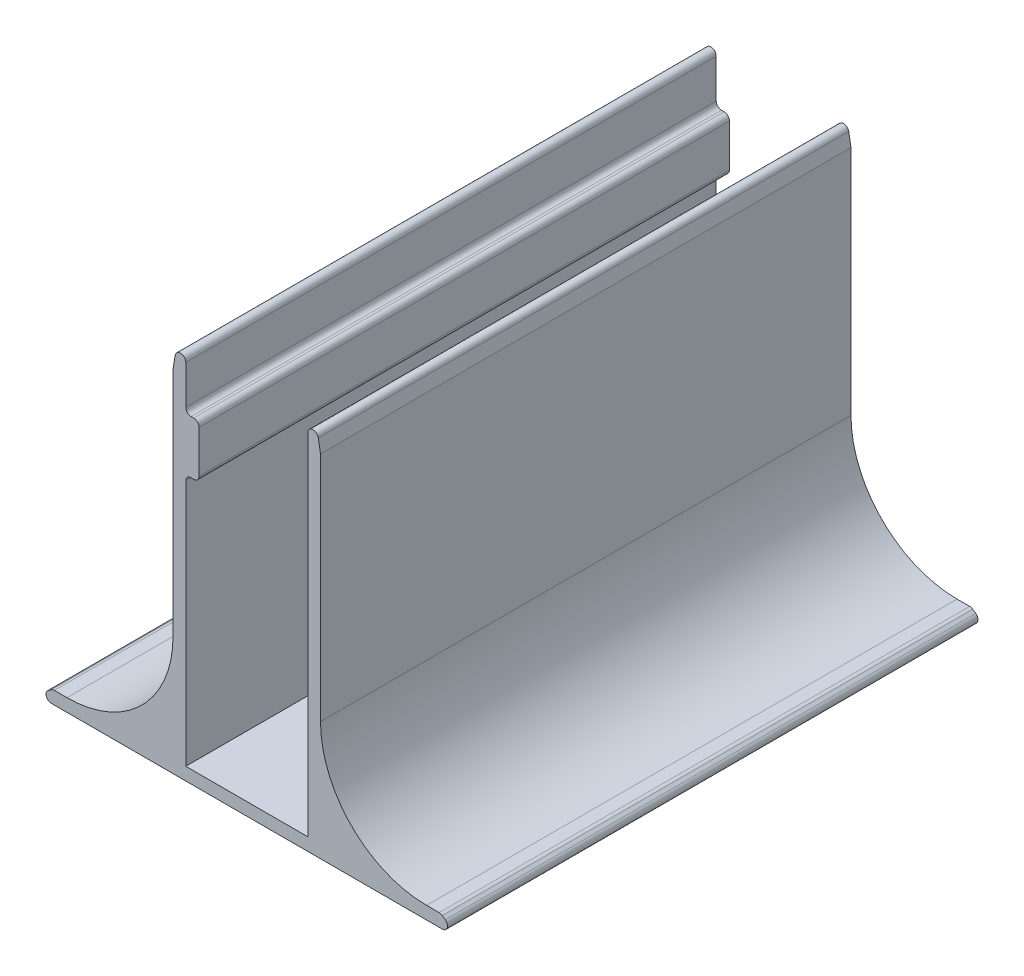
SolidWorks part; units mm, degrees
ref_plane "Plan de face" through (0, 0, 0) normal (0, 0, 1) x (1, 0, 0)
ref_plane "Plan de dessus" through (0, 0, 0) normal (0, 1, 0) x (1, 0, 0)
ref_plane "Plan de droite" through (0, 0, 0) normal (1, 0, 0) x (0, 0, -1)
sketch "Esquisse1" plane through (0, 0, 0) normal (0, 0, 1) x (1, 0, 0)
  line L0 (-11.5, 2.4) -> (11.5, 2.4)
  line L1 (11.5, 2.4) -> (11.5, 80)
  line L3 (40, 0) -> (-40, 0)
  line L4 (0, 0) -> (0, 138.9113) construction
  line L5 (-11.5, 2.4) -> (-11.5, 50)
  line L7 (-11.5, 50) -> (-9, 50)
  line L8 (-9, 50) -> (-9, 60)
  line L9 (-9, 60) -> (-11.5, 60)
  line L10 (-11.5, 60) -> (-11.5, 80)
  line L11 (13.9, 66.1116) -> (13.9, 2.4)
  line L12 (13.9, 2.4) -> (36.5973, 2.4)
  line L14 (-13.9, 2.4) -> (-36.5973, 2.4)
  line L15 (-13.9, 66.1116) -> (-13.9, 2.4)
  line L17 (-11.5, 80) -> (-13.9, 66.1116)
  line L18 (-36.5973, 2.4) -> (-40, 0)
  line L19 (40, 0) -> (36.5973, 2.4)
  line L20 (11.5, 80) -> (13.9, 66.1116)
  point P3 (0, 2.4)
  dimension "D1" = 23
  dimension "D2" = 80
  dimension "D3" = 80
  dimension "D4" = 2.4
  dimension "D5" = 2.5
  dimension "D6" = 10
  dimension "D7" = 20
  dimension "D8" = 2.4
  dimension "D10" = 2.4
extrude "Boss.-Extru.1" add sketch "Esquisse1" along normal blind 100
fillet "Congé2" radius 1 4 edges at (-11.5, 60, 50) (-9, 60, 50) (-9, 50, 50) (-11.5, 50, 50)
fillet "Conges_base" radius 20 2 edges at (13.9, 2.4, 50) (-13.9, 2.4, 50)
fillet "Congé4" radius 1 6 edges at (11.5, 80, 50) (-11.5, 80, 50) (40, 0, 50) (-40, 0, 50) (-36.5973, 2.4, 50) (36.5973, 2.4, 50)
equation "\"ep\"= 2.4"
equation "\"D4@Esquisse1\"=\"ep\""
equation "\"D10@Esquisse1\"=\"ep\""
equation "\"D8@Esquisse1\"=\"ep\""
